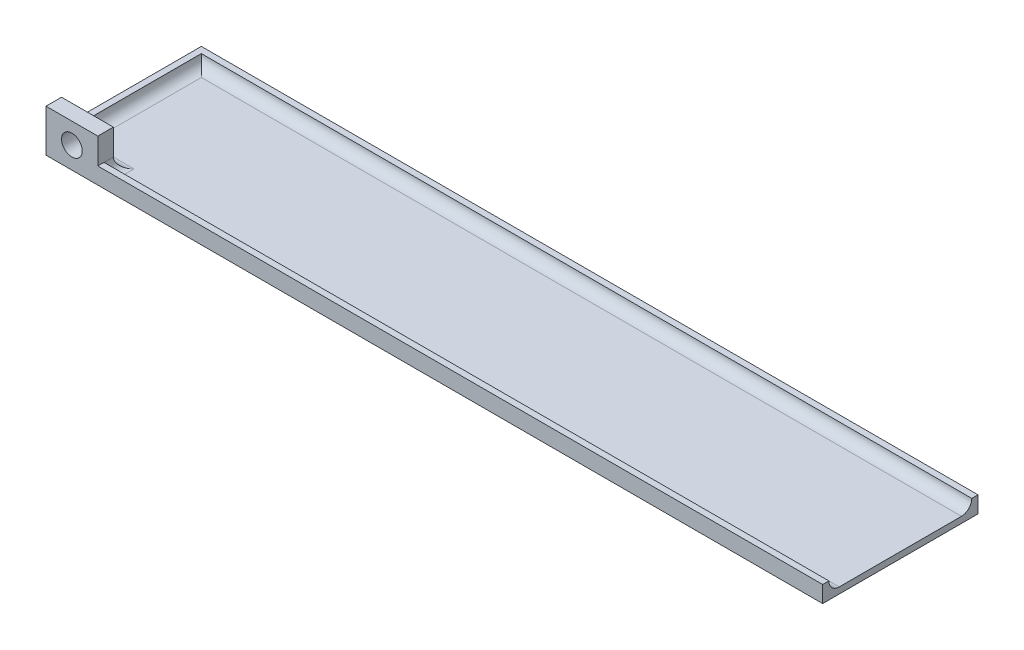
SolidWorks part; units mm, degrees
ref_plane "前视基准面" through (0, 0, 0) normal (0, 0, 1) x (1, 0, 0)
ref_plane "上视基准面" through (0, 0, 0) normal (0, 1, 0) x (1, 0, 0)
ref_plane "右视基准面" through (0, 0, 0) normal (1, 0, 0) x (0, 0, -1)
other "Configuration Table"
sketch "草图1" plane through (0, 0, 0) normal (0, 1, 0) x (1, 0, 0)
  line L1 (-75, 15) -> (75, 15)
  line L2 (-75, 15) -> (-75, -15)
  line L3 (-75, -15) -> (75, -15)
  line L4 (75, 15) -> (75, -15)
  line L5 (-75, 15) -> (75, -15) construction
  line L6 (-75, -15) -> (75, 15) construction
  point P0 (0, 0)
  dimension "D1" = 150
  dimension "D2" = 30
extrude "凸台-拉伸1" add sketch "草图1" along normal blind 1.2
sketch "草图2" plane through (0, 1.2, 0) normal (0, 1, 0) x (1, 0, 0)
  line L0 (75, -15) -> (75, 15) construction
  line L1 (-75, 15) -> (75, 15)
  line L2 (-75, 15) -> (-75, 13.8)
  line L3 (-75, 13.8) -> (75, 13.8)
  line L4 (75, 15) -> (75, 13.8)
  line L6 (-75, -15) -> (75, -15)
  line L7 (-75, -15) -> (-75, -13.8)
  line L8 (-75, -13.8) -> (75, -13.8)
  line L9 (75, -15) -> (75, -13.8)
  dimension "D1" = 1.2
  dimension "D2" = 1.2
extrude "凸台-拉伸2" add sketch "草图2" along normal blind 2
sketch "草图4" plane through (0, 1.2, 0) normal (0, 1, 0) x (1, 0, 0)
  line L0 (-75, 13.8) -> (-75, -13.8) construction
  line L1 (-75, -12) -> (-65, -12)
  line L2 (-75, -12) -> (-75, -15)
  line L3 (-75, -15) -> (-65, -15)
  line L4 (-65, -12) -> (-65, -15)
  line L5 (-75, -15) -> (75, -15) construction
  dimension "D1" = 10
  dimension "D2" = 3
extrude "凸台-拉伸3" add sketch "草图4" along normal blind 7
sketch "草图5" plane through (0, 0, 15) normal (0, 0, 1) x (1, 0, 0)
  line L0 (-70, 8.2) -> (-70, 0) construction
  line L1 (-75, 8.2) -> (-65, 8.2) construction
  line L2 (-75, 0) -> (75, 0) construction
  circle A0 centre (-70, 4.2) radius 2
  dimension "D1" = 4
  dimension "D2" = 4
extrude "切除-拉伸1" cut sketch "草图5" against normal blind 10
sketch "草图6" plane through (0, 1.2, 0) normal (0, 1, 0) x (1, 0, 0)
  line L0 (-65, -12) -> (-75, -12) construction
  line L1 (-75, 15) -> (-73.8, 15)
  line L2 (-75, 15) -> (-75, -12)
  line L3 (-75, -12) -> (-73.8, -12)
  line L4 (-73.8, 15) -> (-73.8, -12)
  dimension "D1" = 1.2
extrude "凸台-拉伸4" add sketch "草图6" along normal blind 2
fillet "圆角1" radius 2 5 edges at (-69.4, 1.2, 12) (-65, 1.2, 12.9) (0.6, 1.2, -13.8) (-73.8, 1.2, -0.9) (5, 1.2, 13.8)
